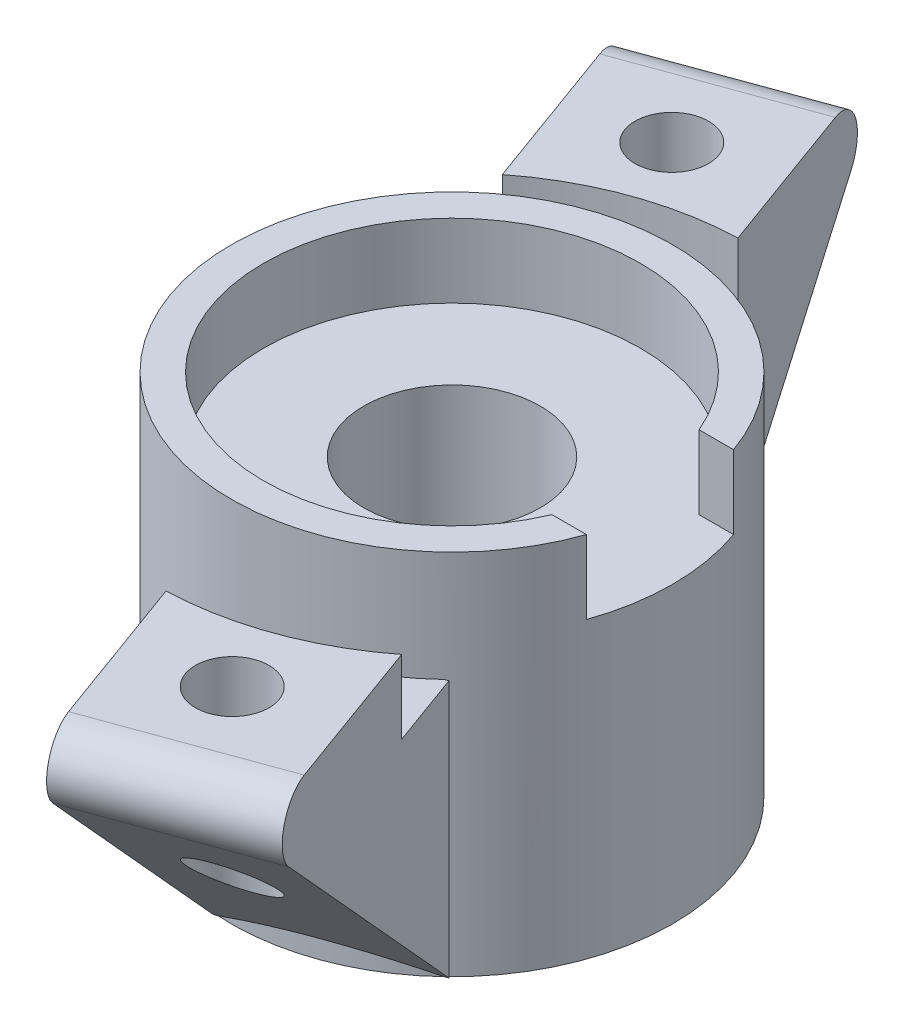
SolidWorks part; units mm, degrees
ref_plane "Front Plane" through (0, 0, 0) normal (0, 0, 1) x (1, 0, 0)
ref_plane "Top Plane" through (0, 0, 0) normal (0, 1, 0) x (1, 0, 0)
ref_plane "Right Plane" through (0, 0, 0) normal (1, 0, 0) x (0, 0, -1)
sketch "Sketch1" plane through (0, 0, 0) normal (0, 1, 0) x (1, 0, 0)
  circle A0 centre (0, 0) radius 12
  circle A1 centre (0, 0) radius 4.8
extrude "Boss-Extrude2" add sketch "Sketch1" against normal blind 20 contours A0 A1 | A1 region at (-11.6606, 0, 0) region at (0, 0, 0)
extrude "Cut-Extrude2" cut sketch "Sketch1<3>" against normal through all contours A1 region at (0, 0, 0)
sketch "Sketch1<3>" plane through (0, 0, 0) normal (0, 1, 0) x (1, 0, 0) same geometry as "Sketch1"
sketch "Sketch3" plane through (0, 0, 0) normal (0, 1, 0) x (1, 0, 0)
  circle A0 centre (0, 0) radius 10.25
extrude "Cut-Extrude3" cut sketch "Sketch3" against normal blind 4
sketch "Sketch5" plane through (0, 0, 0) normal (0, 1, 0) x (1, 0, 0)
  line L0 (-11, 0) -> (11, 0) construction
  line L1 (5.4486, -4) -> (16.4836, -4)
  line L2 (5.4486, -4) -> (5.4486, 4)
  line L3 (5.4486, 4) -> (16.4836, 4)
  line L4 (16.4836, -4) -> (16.4836, 4)
  line L5 (5.4486, -4) -> (16.4836, 4) construction
  line L6 (5.4486, 4) -> (16.4836, -4) construction
  point P0 (10.9661, 0)
  dimension "D1" = 8
extrude "Cut-Extrude5" cut sketch "Sketch5" against normal up to surface (4 mm away) up to face at (0, -4, 10.25)
ref_axis "Axis1" through (0, 1, 0) along (0, -1, 0)
ref_plane "Plane1" through (0, 0, 0) normal (-0.9397, 0, 0.342) x (0, -1, 0)
sketch "Sketch6" plane through (0, 0, 0) normal (-0.9397, 0, 0.342) x (0, -1, 0)
  line L0 (2, -11) -> (20, -11)
  line L1 (20, -11) -> (2, -29)
  line L2 (2, -29) -> (2, -11)
  line L3 (-1, 0) -> (21, 0) construction
  line L4 (20, -12) -> (20, 12) construction
  line L5 (0, 14.1073) -> (0, -14.1073) construction
  dimension "D1" = 11
  dimension "D2" = 45
  dimension "D3" = 2
extrude "Boss-Extrude3" add sketch "Sketch6" along normal blind 5 and the other way blind 5
sketch "Sketch7" plane through (0, 0, 0) normal (0, 1, 0) x (1, 0, 0)
  circle A0 centre (0, 0) radius 12
  circle A1 centre (0, 0) radius 16.1
extrude "Cut-Extrude6" cut sketch "Sketch7" against normal blind 6
sketch "Sketch9" plane through (0, -2, 0) normal (0, 1, 0) x (1, 0, 0)
  line L0 (-4.8922, 13.4411) -> (4.8922, -13.4411) construction
  circle A0 centre (-6.8404, 18.7939) radius 2
  dimension "D1" = 20
extrude "Cut-Extrude7" cut sketch "Sketch9" against normal up to next
fillet "Fillet1" radius 2 1 edges at (-9.9186, -2, -27.2511)
ref_plane "Plane2" through (0, 0, 0) normal (-0.342, 0, -0.9397) x (0, -1, 0)
mirror "Mirror1" about plane through (0, 0, 0) normal (-0.342, 0, -0.9397) of "Fillet1", "Cut-Extrude7", "Cut-Extrude6", "Boss-Extrude3"
